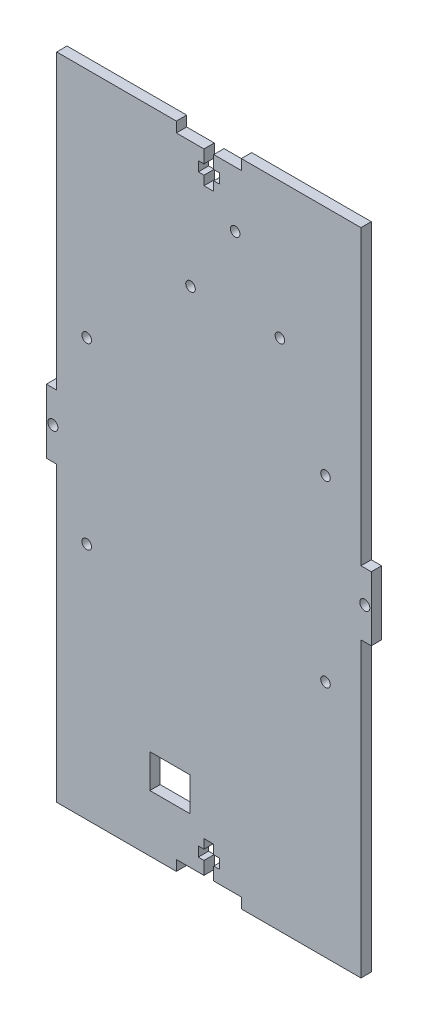
SolidWorks part; units mm, degrees
ref_plane "Front Plane" through (0, 0, 0) normal (0, 0, 1) x (1, 0, 0)
ref_plane "Top Plane" through (0, 0, 0) normal (0, 1, 0) x (1, 0, 0)
ref_plane "Right Plane" through (0, 0, 0) normal (1, 0, 0) x (0, 0, -1)
sketch "Sketch1" plane through (0, 0, 0) normal (0, 0, 1) x (1, 0, 0)
  line L0 (0, 40) -> (0, -40) construction
  line L5 (-50, -100) -> (50, 100) construction
  line L6 (-50, 100) -> (50, -100) construction
  line L7 (-100, 0) -> (100, 0) construction
  line L32 (-50, 100) -> (50, 100)
  line L35 (50, 100) -> (50, -100)
  line L36 (50, -100) -> (-50, -100)
  line L37 (-50, -100) -> (-50, 100)
  point P0 (0, 0)
  dimension "D1" = 100
  dimension "D2" = 200
extrude "Boss-Extrude2" add sketch "Sketch1" along normal blind 3.18
sketch "Sketch2" plane through (0, 0, 3.18) normal (0, 0, 1) x (1, 0, 0)
  line L0 (0, -100) -> (0, 100) construction
  line L1 (-123.0225, 0) -> (147.0753, 0) construction
  line L2 (50, 100) -> (-50, 100) construction
  line L4 (-10, 100) -> (-10, 96.82)
  line L5 (-10, 96.82) -> (-1.5, 96.82)
  line L6 (10, 100) -> (10, 96.82)
  line L7 (1.5, 96.82) -> (10, 96.82)
  line L9 (-1.5, 96.82) -> (-1.5, 92.82)
  line L10 (-1.5, 87) -> (1.5, 87)
  line L11 (1.5, 96.82) -> (1.5, 92.82)
  line L12 (-3.25, 92.82) -> (-1.5, 92.82)
  line L13 (-3.25, 92.82) -> (-3.25, 89.82)
  line L14 (-3.25, 89.82) -> (-1.5, 89.82)
  line L15 (3.25, 92.82) -> (3.25, 89.82)
  line L16 (1.5, 92.82) -> (3.25, 92.82)
  line L17 (-1.5, 89.82) -> (-1.5, 87)
  line L18 (1.5, 89.82) -> (1.5, 87)
  line L19 (1.5, 89.82) -> (3.25, 89.82)
  line L20 (-10, 100) -> (10, 100)
  line L21 (-50, -100) -> (50, -100) construction
  line L22 (-50, 100) -> (-50, -100) construction
  line L23 (-50, 9.875) -> (-46.82, 9.875)
  line L24 (-50, 9.875) -> (-50, 100)
  line L25 (-50, 100) -> (-46.82, 100)
  line L26 (-46.82, 9.875) -> (-46.82, 100)
  line L28 (-50, -9.875) -> (-46.82, -9.875)
  line L29 (-50, -9.875) -> (-50, -100)
  line L30 (-50, -100) -> (-46.82, -100)
  line L31 (-46.82, -9.875) -> (-46.82, -100)
  circle A0 centre (-48, 0) radius 1.55
  dimension "D11" = 3.1
  dimension "D12" = 2
  dimension "D1" = 4
  dimension "D2" = 3
  dimension "D3" = 3
  dimension "D4" = 20
  dimension "D5" = 6.5
  dimension "D6" = 3.18
  dimension "D7" = 13
  dimension "D8" = 19.75
  dimension "D9" = 3.18
  dimension "D10" = 3.18
extrude "Cut-Extrude1" cut sketch "Sketch2" against normal through all
mirror "Mirror1" about plane through (0, 0, 0) normal (0, 1, 0) of "Cut-Extrude1"
mirror "Mirror3" about plane through (0, 0, 0) normal (1, 0, 0) of "Cut-Extrude1"
sketch "Sketch4" plane through (0, 0, 3.18) normal (0, 0, 1) x (1, 0, 0)
  line L5 (-18.15, -82.52) -> (-5.7964, -82.52)
  line L6 (-18.15, -82.52) -> (-18.15, -72.1664)
  line L7 (-18.15, -72.1664) -> (-5.7964, -72.1664)
  line L8 (-5.7964, -82.52) -> (-5.7964, -72.1664)
  arc A0 (-5.65, -72.52) -> (-6.15, -72.02) centre (-6.15, -72.52) ccw construction
extrude "Cut-Extrude3" cut sketch "Sketch4" against normal through all
sketch "Sketch5" plane through (0, 0, 3.18) normal (0, 0, 1) x (1, 0, 0)
  circle A0 centre (-37.5809, 28.4641) radius 1.47
  circle A1 centre (35.9045, 28.4641) radius 1.47
  circle A2 centre (-37.5809, -26.5359) radius 1.47
  circle A3 centre (35.9045, -26.5359) radius 1.47
  circle A4 centre (-37.5809, 28.4641) radius 1.47 construction
  circle A5 centre (35.9045, 28.4641) radius 1.47 construction
  circle A6 centre (35.9045, -26.5359) radius 1.47 construction
  circle A8 centre (-37.5809, -26.5359) radius 1.47 construction
extrude "Cut-Extrude4" cut sketch "Sketch5" against normal through all
sketch "Sketch6" plane through (0, 0, 3.18) normal (0, 0, 1) x (1, 0, 0)
  circle A0 centre (-5.6383, 58.12) radius 1.47
  circle A1 centre (8.1117, 79.62) radius 1.47
  circle A2 centre (21.8617, 58.12) radius 1.47
  circle A3 centre (-5.6383, 58.12) radius 1.4 construction
  circle A4 centre (8.1117, 79.62) radius 1.4 construction
  circle A5 centre (21.8617, 58.12) radius 1.4 construction
  dimension "D1" = 2.94
extrude "Cut-Extrude5" cut sketch "Sketch6" against normal through all
